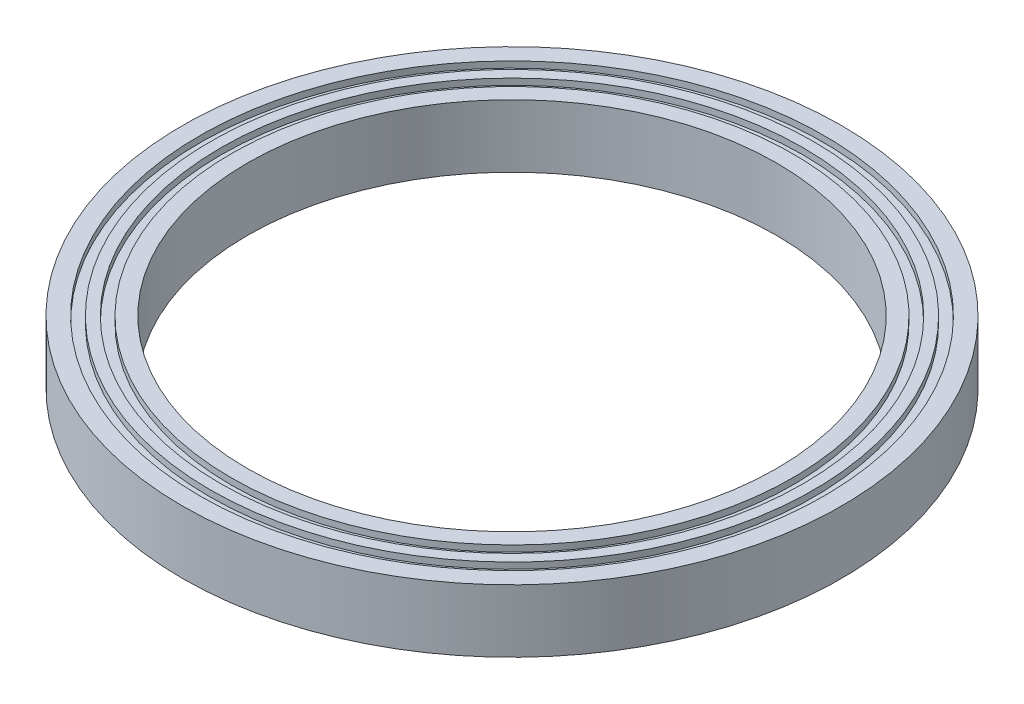
SolidWorks part; units mm, degrees
ref_plane "Front Plane" through (0, 0, 0) normal (0, 0, 1) x (1, 0, 0)
ref_plane "Top Plane" through (0, 0, 0) normal (0, 1, 0) x (1, 0, 0)
ref_plane "Right Plane" through (0, 0, 0) normal (1, 0, 0) x (0, 0, -1)
sketch "Sketch1" plane through (0, 0, 0) normal (0, 1, 0) x (1, 0, 0)
  circle A0 centre (0, 0) radius 9945
  circle A1 centre (0, 0) radius 8945
  dimension "D1" = 19890
  dimension "D2" = 17890
  dimension "D3" = 1000
extrude "Boss-Extrude1" add sketch "Sketch1" along normal blind 600
sketch "Sketch2" plane through (0, 0, 0) normal (0, 1, 0) x (1, 0, 0)
  circle A0 centre (0, 0) radius 8890
  circle A1 centre (0, 0) radius 9945
  dimension "D1" = 17780
  dimension "D2" = 19890
extrude "Boss-Extrude5" add sketch "Sketch2" along normal mid plane 2000
sketch "Sketch3" plane through (0, 1000, 0) normal (0, 1, 0) x (1, 0, 0)
  circle A0 centre (0, 0) radius 8945
  circle A1 centre (0, 0) radius 9275
  dimension "D1" = 17890
  dimension "D2" = 18550
extrude "Cut-Extrude1" cut sketch "Sketch3" against normal blind 200
sketch "Sketch4" plane through (0, 1000, 0) normal (0, 1, 0) x (1, 0, 0)
  circle A0 centre (0, 0) radius 9611.5
  circle A1 centre (0, 0) radius 9945
  circle A2 centre (0, 0) radius 9275 construction
  circle A3 centre (0, 0) radius 8945 construction
  dimension "D1" = 19223
  dimension "D2" = 19890
  dimension "D3" = 333.5
  dimension "D4" = 330
extrude "Cut-Extrude2" cut sketch "Sketch4" against normal blind 200
sketch "Sketch5" plane through (0, 0, 0) normal (0, 1, 0) x (1, 0, 0)
  circle A0 centre (0, 0) radius 10500
  circle A1 centre (0, 0) radius 9945
  dimension "D1" = 19890
extrude "Boss-Extrude6" add sketch "Sketch5" along normal mid plane 2000
sketch "Sketch6" plane through (0, 0, 0) normal (0, 1, 0) x (1, 0, 0)
  circle A0 centre (0, 0) radius 8890
  circle A1 centre (0, 0) radius 8431.0025
extrude "Boss-Extrude7" add sketch "Sketch6" along normal mid plane 2000
sketch "Sketch7" plane through (0, -1000, 0) normal (0, -1, 0) x (1, 0, 0)
  circle A1 centre (0, 0) radius 8945
  circle A2 centre (0, 0) radius 9945
  dimension "D1" = 19890
extrude "Cut-Extrude3" cut sketch "Sketch7" against normal blind 1000
